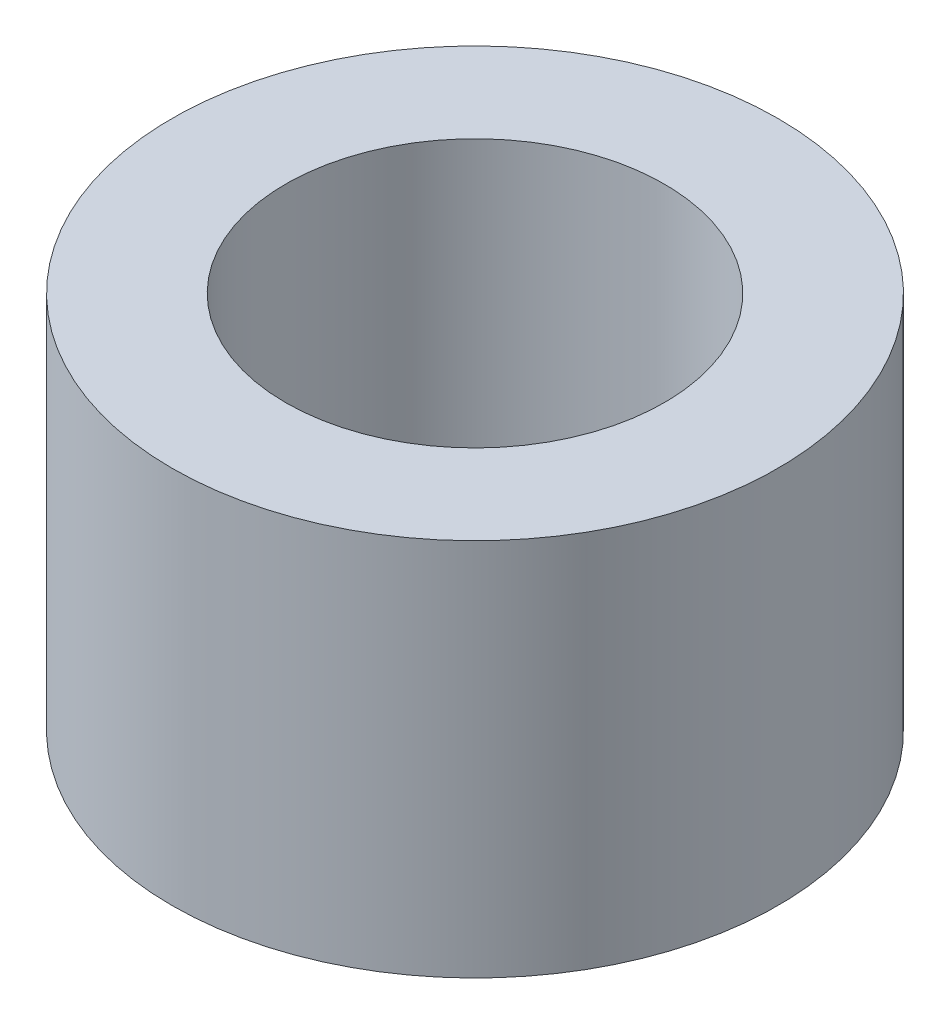
SolidWorks part; units mm, degrees
ref_plane "Front Plane" through (0, 0, 0) normal (0, 0, 1) x (1, 0, 0)
ref_plane "Top Plane" through (0, 0, 0) normal (0, 1, 0) x (1, 0, 0)
ref_plane "Right Plane" through (0, 0, 0) normal (1, 0, 0) x (0, 0, -1)
sketch "Sketch2" plane through (0, 0, 0) normal (0, 1, 0) x (1, 0, 0)
  circle A0 centre (0, 0) radius 4
  circle A1 centre (0, 0) radius 2.5
  dimension "D1" = 8
  dimension "D2" = 5
extrude "Boss-Extrude1" add sketch "Sketch2" along normal blind 5
